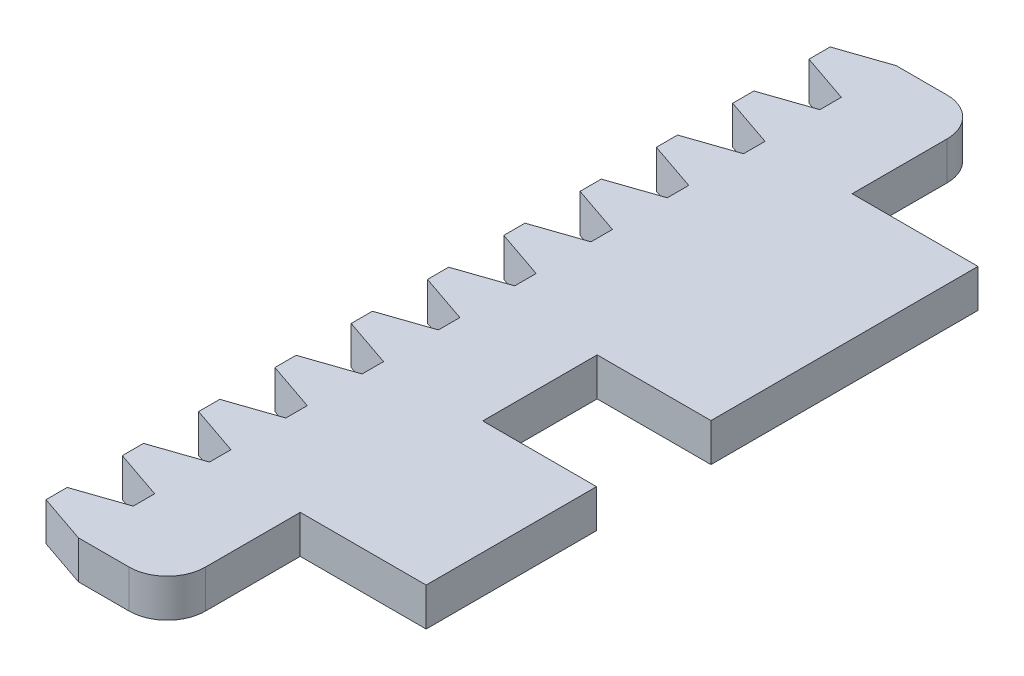
SolidWorks part; units mm, degrees
ref_plane "Front Plane" through (0, 0, 0) normal (0, 0, 1) x (1, 0, 0)
ref_plane "Top Plane" through (0, 0, 0) normal (0, 1, 0) x (1, 0, 0)
ref_plane "Right Plane" through (0, 0, 0) normal (1, 0, 0) x (0, 0, -1)
sketch "Sketch1" plane through (0, 0, 0) normal (0, 1, 0) x (1, 0, 0)
  line L4 (37.95, 21.7) -> (28.05, 21.7) construction
  line L5 (28.05, 29.157) -> (28.05, 21.7) construction
  line L6 (21.0585, 32.157) -> (25.05, 32.157) construction
  line L7 (21.0585, 32.157) -> (17.1887, 30.8335) construction
  line L8 (17.1887, 30.8335) -> (17.1887, 29.1665) construction
  line L13 (17.1887, 29.1665) -> (21.0585, 27.843) construction
  line L14 (21.0585, 26.157) -> (21.0585, 27.843) construction
  line L15 (21.0585, 26.157) -> (17.1887, 24.8335) construction
  line L16 (17.1887, 24.8335) -> (17.1887, 23.1665) construction
  line L17 (17.1887, 23.1665) -> (21.0585, 21.843) construction
  line L18 (21.0585, 20.157) -> (21.0585, 21.843) construction
  line L19 (21.0585, 20.157) -> (17.1887, 18.8335) construction
  line L20 (17.1887, 18.8335) -> (17.1887, 17.1665) construction
  line L21 (17.1887, 17.1665) -> (21.0585, 15.843) construction
  line L22 (21.0585, 14.157) -> (21.0585, 15.843) construction
  line L23 (21.0585, 14.157) -> (17.1887, 12.8335) construction
  line L24 (17.1887, 12.8335) -> (17.1887, 11.1665) construction
  line L25 (17.1887, 11.1665) -> (21.0585, 9.843) construction
  line L26 (21.0585, 8.157) -> (21.0585, 9.843) construction
  line L27 (21.0585, 8.157) -> (17.1887, 6.8335) construction
  line L28 (17.1887, 6.8335) -> (17.1887, 5.1665) construction
  line L29 (17.1887, 5.1665) -> (21.0585, 3.843) construction
  line L30 (21.0585, 2.157) -> (21.0585, 3.843) construction
  line L31 (21.0585, 2.157) -> (17.1887, 0.8335) construction
  line L32 (17.1887, 0.8335) -> (17.1887, -0.8335) construction
  line L33 (17.1887, -0.8335) -> (21.0585, -2.157) construction
  line L34 (21.0585, -3.843) -> (21.0585, -2.157) construction
  line L35 (21.0585, -3.843) -> (17.1887, -5.1665) construction
  line L36 (17.1887, -5.1665) -> (17.1887, -6.8335) construction
  line L37 (17.1887, -6.8335) -> (21.0585, -8.157) construction
  line L38 (21.0585, -9.843) -> (21.0585, -8.157) construction
  line L39 (21.0585, -9.843) -> (17.1887, -11.1665) construction
  line L40 (17.1887, -11.1665) -> (17.1887, -12.8335) construction
  line L41 (17.1887, -12.8335) -> (21.0585, -14.157) construction
  line L42 (21.0585, -15.843) -> (21.0585, -14.157) construction
  line L43 (21.0585, -15.843) -> (17.1887, -17.1665) construction
  line L44 (17.1887, -17.1665) -> (17.1887, -18.8335) construction
  line L45 (17.1887, -18.8335) -> (21.0585, -20.157) construction
  line L46 (21.0585, -21.843) -> (21.0585, -20.157) construction
  line L47 (21.0585, -21.843) -> (17.1887, -23.1665) construction
  line L48 (17.1887, -23.1665) -> (17.1887, -24.8335) construction
  line L49 (17.1887, -24.8335) -> (21.0585, -26.157) construction
  line L55 (21.0585, -27.843) -> (21.0585, -26.157) construction
  line L56 (21.0585, -27.843) -> (17.1887, -29.1665) construction
  line L57 (17.1887, -29.1665) -> (17.1887, -30.8335) construction
  line L99 (17.1887, -30.8335) -> (21.0585, -32.157) construction
  line L100 (25.05, -32.157) -> (21.0585, -32.157) construction
  line L105 (28.05, -21.7) -> (28.05, -29.157) construction
  line L107 (37.95, -21.7) -> (28.05, -21.7) construction
  line L108 (37.95, -8.3) -> (37.95, -21.7) construction
  line L109 (29, -8.3) -> (37.95, -8.3) construction
  line L110 (29, 0.7) -> (29, -8.3) construction
  line L111 (37.95, 0.7) -> (29, 0.7) construction
  line L112 (37.95, 21.7) -> (37.95, 0.7) construction
  line L113 (37.95, 21.7) -> (28.05, 21.7)
  line L114 (28.05, 29.157) -> (28.05, 21.7)
  line L115 (21.0585, 32.157) -> (25.05, 32.157)
  line L116 (21.0585, 32.157) -> (17.1887, 30.8335)
  line L117 (17.1887, 30.8335) -> (17.1887, 29.1665)
  line L118 (17.1887, 29.1665) -> (21.0585, 27.843)
  line L119 (21.0585, 26.157) -> (21.0585, 27.843)
  line L120 (21.0585, 26.157) -> (17.1887, 24.8335)
  line L121 (17.1887, 24.8335) -> (17.1887, 23.1665)
  line L122 (17.1887, 23.1665) -> (21.0585, 21.843)
  line L123 (21.0585, 20.157) -> (21.0585, 21.843)
  line L124 (21.0585, 20.157) -> (17.1887, 18.8335)
  line L125 (17.1887, 18.8335) -> (17.1887, 17.1665)
  line L126 (17.1887, 17.1665) -> (21.0585, 15.843)
  line L127 (21.0585, 14.157) -> (21.0585, 15.843)
  line L128 (21.0585, 14.157) -> (17.1887, 12.8335)
  line L129 (17.1887, 12.8335) -> (17.1887, 11.1665)
  line L130 (17.1887, 11.1665) -> (21.0585, 9.843)
  line L131 (21.0585, 8.157) -> (21.0585, 9.843)
  line L132 (21.0585, 8.157) -> (17.1887, 6.8335)
  line L133 (17.1887, 6.8335) -> (17.1887, 5.1665)
  line L134 (17.1887, 5.1665) -> (21.0585, 3.843)
  line L135 (21.0585, 2.157) -> (21.0585, 3.843)
  line L136 (21.0585, 2.157) -> (17.1887, 0.8335)
  line L137 (17.1887, 0.8335) -> (17.1887, -0.8335)
  line L138 (17.1887, -0.8335) -> (21.0585, -2.157)
  line L139 (21.0585, -3.843) -> (21.0585, -2.157)
  line L140 (21.0585, -3.843) -> (17.1887, -5.1665)
  line L141 (17.1887, -5.1665) -> (17.1887, -6.8335)
  line L142 (17.1887, -6.8335) -> (21.0585, -8.157)
  line L143 (21.0585, -9.843) -> (21.0585, -8.157)
  line L144 (21.0585, -9.843) -> (17.1887, -11.1665)
  line L145 (17.1887, -11.1665) -> (17.1887, -12.8335)
  line L146 (17.1887, -12.8335) -> (21.0585, -14.157)
  line L147 (21.0585, -15.843) -> (21.0585, -14.157)
  line L148 (21.0585, -15.843) -> (17.1887, -17.1665)
  line L149 (17.1887, -17.1665) -> (17.1887, -18.8335)
  line L150 (17.1887, -18.8335) -> (21.0585, -20.157)
  line L151 (21.0585, -21.843) -> (21.0585, -20.157)
  line L152 (21.0585, -21.843) -> (17.1887, -23.1665)
  line L153 (17.1887, -23.1665) -> (17.1887, -24.8335)
  line L154 (17.1887, -24.8335) -> (21.0585, -26.157)
  line L155 (21.0585, -27.843) -> (21.0585, -26.157)
  line L156 (21.0585, -27.843) -> (17.1887, -29.1665)
  line L157 (17.1887, -29.1665) -> (17.1887, -30.8335)
  line L160 (17.1887, -30.8335) -> (21.0585, -32.157)
  line L161 (25.05, -32.157) -> (21.0585, -32.157)
  line L162 (28.05, -21.7) -> (28.05, -29.157)
  line L163 (37.95, -21.7) -> (28.05, -21.7)
  line L164 (37.95, -8.3) -> (37.95, -21.7)
  line L165 (29, -8.3) -> (37.95, -8.3)
  line L166 (29, 0.7) -> (29, -8.3)
  line L167 (37.95, 0.7) -> (29, 0.7)
  line L168 (37.95, 21.7) -> (37.95, 0.7)
  line L169 (37.95, 28.7) -> (33.35, 28.7) construction
  line L170 (15.05, 32.157) -> (26.5, 32.157) construction
  line L171 (15.05, 32.157) -> (15.05, -32.157) construction
  line L172 (15.05, -32.157) -> (26.5, -32.157) construction
  line L173 (19.65, 32.157) -> (19.65, -32.157) construction
  line L174 (37.95, 28.7) -> (33.35, 28.7) construction
  line L175 (37.95, 28.7) -> (37.95, -28.7) construction
  line L176 (37.95, -28.7) -> (33.35, -28.7) construction
  line L177 (33.35, 28.7) -> (33.35, -28.7) construction
  line L178 (21.0585, 32.157) -> (15.05, 32.157) construction
  line L179 (15.05, -32.157) -> (21.0585, -32.157) construction
  line L180 (15.05, 32.157) -> (15.05, -32.157) construction
  line L181 (19.65, -32.157) -> (19.65, 32.157) construction
  line L182 (37.95, -28.7) -> (33.35, -28.7) construction
  line L183 (33.35, -28.7) -> (33.35, 28.7) construction
  line L184 (37.95, 28.7) -> (37.95, -28.7) construction
  line L185 (37.95, 0) -> (15.05, 0) construction
  line L186 (15.05, 0) -> (37.95, 0) construction
  line L187 (26.5, 32.157) -> (26.5, -32.157) construction
  line L188 (26.5, 32.157) -> (26.5, -32.157) construction
  line L189 (19.65, 21.7) -> (37.95, 21.7) construction
  line L190 (19.65, -21.7) -> (37.95, -21.7) construction
  line L191 (37.95, 21.7) -> (19.65, 21.7) construction
  line L192 (37.95, -2.3) -> (32, -2.3) construction
  line L193 (32, -2.3) -> (32, -5.3) construction
  line L194 (32, -5.3) -> (37.95, -5.3) construction
  line L195 (29, -3.8) -> (37.95, -3.8) construction
  line L196 (34.95, 0.7) -> (34.95, 18.7) construction
  line L197 (34.95, -8.3) -> (34.95, -18.7) construction
  line L198 (34.95, 18.7) -> (19.65, 18.7) construction
  line L199 (19.65, -18.7) -> (34.95, -18.7) construction
  line L200 (34.95, 18.7) -> (34.95, 21.7) construction
  line L201 (34.95, 18.7) -> (37.95, 18.7) construction
  line L202 (34.95, -18.7) -> (37.95, -18.7) construction
  line L203 (34.95, -18.7) -> (34.95, -21.7) construction
  line L204 (37.15, 28.7) -> (37.15, -28.7) construction
  line L205 (34.15, 28.7) -> (34.15, -28.7) construction
  line L206 (18.85, 32.157) -> (18.85, -32.157) construction
  line L207 (15.85, 32.157) -> (15.85, -32.157) construction
  line L208 (37.15, 28.7) -> (37.15, 0.7) construction
  line L209 (34.15, 28.7) -> (34.15, 0.7) construction
  line L210 (18.85, 32.157) -> (18.85, -32.157) construction
  line L211 (15.85, 32.157) -> (15.85, -32.157) construction
  line L212 (37.15, -8.3) -> (37.15, -28.7) construction
  line L213 (34.15, -8.3) -> (34.15, -28.7) construction
  arc A2 (28.05, 29.157) -> (25.05, 32.157) centre (25.05, 29.157) ccw construction
  arc A3 (25.05, -32.157) -> (28.05, -29.157) centre (25.05, -29.157) ccw construction
  arc A4 (28.05, 29.157) -> (25.05, 32.157) centre (25.05, 29.157) ccw
  arc A5 (25.05, -32.157) -> (28.05, -29.157) centre (25.05, -29.157) ccw
sketch "Sketch2" plane through (0, 0, 0) normal (0, 0, 1) x (1, 0, 0)
  line L1 (37.95, -3) -> (15.05, -3)
  line L2 (37.95, -3) -> (37.95, 0)
  line L3 (37.95, 0) -> (15.05, 0)
  line L4 (15.05, -3) -> (15.05, 0)
  line L5 (21, -3) -> (-21, -3) construction
extrude "Boss-Extrude1" add sketch "Sketch1" against normal up to vertex (3 mm away) up to point (15.05, -3, 0)
ref_plane "gear" through (0, 0, 2.3) normal (0, 0, 1) x (1, 0, 0)
ref_plane "front" through (0, 0, 21.7) normal (0, 0, 1) x (1, 0, 0)
ref_plane "back" through (0, 0, -21.7) normal (0, 0, 1) x (1, 0, 0)
ref_plane "top" through (37.15, 0, 0) normal (1, 0, 0) x (0, 0, -1)
ref_plane "bottom" through (15.85, 0, 0) normal (1, 0, 0) x (0, 0, -1)
ref_plane "sym" through (26.5, 0, 0) normal (1, 0, 0) x (0, 0, -1)
